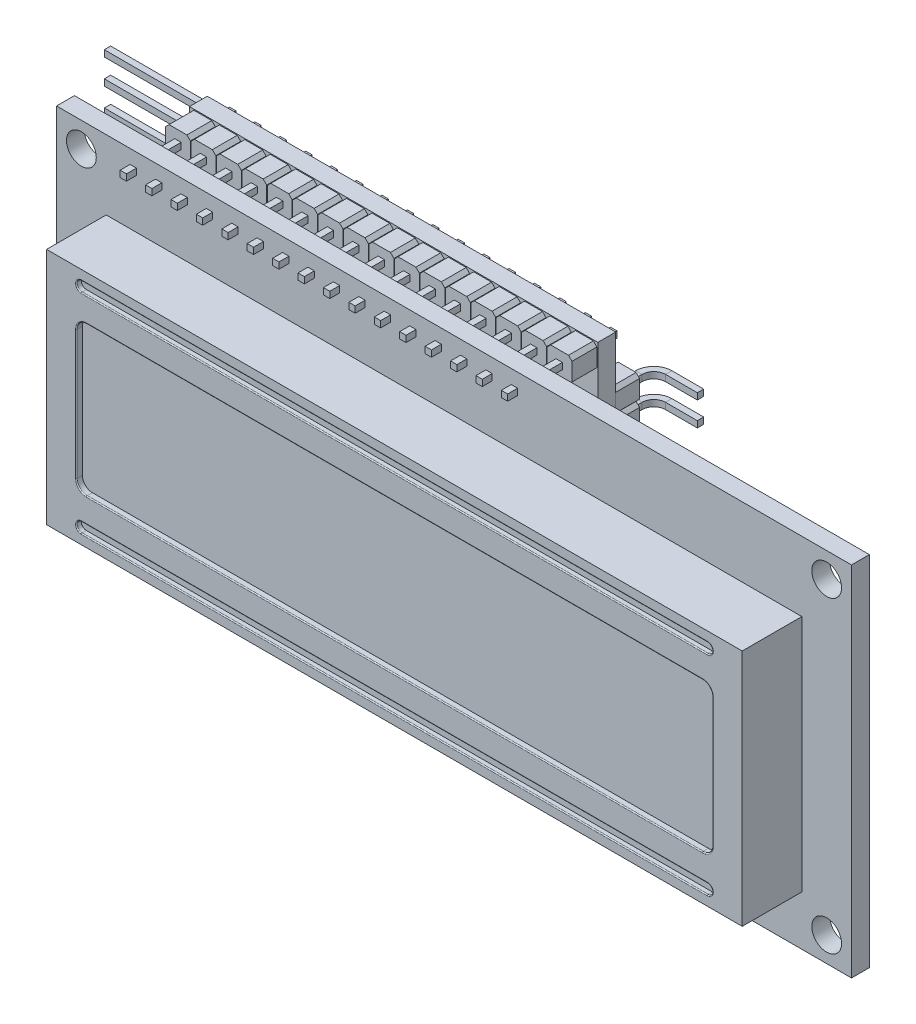
SolidWorks part; units mm, degrees
ref_plane "Front Plane" through (0, 0, 0) normal (0, 0, 1) x (1, 0, 0)
ref_plane "Top Plane" through (0, 0, 0) normal (0, 1, 0) x (1, 0, 0)
ref_plane "Right Plane" through (0, 0, 0) normal (1, 0, 0) x (0, 0, -1)
sketch "Sketch1" plane through (0, 0, 0) normal (0, 0, 1) x (1, 0, 0)
  line L0 (-40, 0) -> (40, 0) construction
  line L1 (-40, 18) -> (40, 18)
  line L2 (-40, 18) -> (-40, -18)
  line L3 (-40, -18) -> (40, -18)
  line L4 (40, 18) -> (40, -18)
  point P6 (0, 0)
  dimension "D1" = 80
  dimension "D2" = 36
extrude "silicon_chip" add sketch "Sketch1" along normal blind 1.8
sketch "Sketch2" plane through (0, 0, 1.8) normal (0, 0, 1) x (1, 0, 0)
  line L0 (40, 18) -> (-40, 18) construction
  line L1 (-40, 18) -> (-40, -18) construction
  line L2 (40, -18) -> (40, 18) construction
  line L3 (-40, -18) -> (40, -18) construction
  circle A0 centre (37.5, 15.5) radius 1.5
  circle A1 centre (37.5, -15.5) radius 1.5
  circle A2 centre (-37.5, -15.5) radius 1.5
  circle A3 centre (-37.5, 15.5) radius 1.5
  point P16 (0, 0)
  point P17 (0, 0)
  point P18 (0, 0)
  point P19 (0, 0)
  dimension "D1" = 3
  dimension "D4" = 2.5
  dimension "D5" = 2.5
  dimension "D2" = 2.5
  dimension "D3" = 2.5
extrude "screw_holes" cut sketch "Sketch2" against normal up to surface (1.8 mm away) up to face at (0, 0, 0)
sketch "Sketch3" plane through (0, 0, 1.8) normal (0, 0, 1) x (1, 0, 0)
  line L0 (-40, 18) -> (-40, -18) construction
  line L1 (-32.6, 16.6) -> (-31.9607, 16.6)
  line L2 (-32.6, 16.6) -> (-32.6, 15.9607)
  line L3 (-32.6, 15.9607) -> (-31.9607, 15.9607)
  line L4 (-31.9607, 16.6) -> (-31.9607, 15.9607)
  line L5 (40, 18) -> (-40, 18) construction
  line L6 (-29.4033, 16.6) -> (-29.4033, 15.9607)
  line L7 (-30.0426, 15.9607) -> (-29.4033, 15.9607)
  line L8 (-30.0426, 16.6) -> (-30.0426, 15.9607)
  line L9 (-30.0426, 16.6) -> (-29.4033, 16.6)
  line L10 (-26.8459, 16.6) -> (-26.8459, 15.9607)
  line L11 (-27.4852, 15.9607) -> (-26.8459, 15.9607)
  line L12 (-27.4852, 16.6) -> (-27.4852, 15.9607)
  line L13 (-27.4852, 16.6) -> (-26.8459, 16.6)
  line L14 (-24.2885, 16.6) -> (-24.2885, 15.9607)
  line L15 (-24.9279, 15.9607) -> (-24.2885, 15.9607)
  line L16 (-24.9279, 16.6) -> (-24.9279, 15.9607)
  line L17 (-24.9279, 16.6) -> (-24.2885, 16.6)
  line L18 (-21.7311, 16.6) -> (-21.7311, 15.9607)
  line L19 (-22.3705, 15.9607) -> (-21.7311, 15.9607)
  line L20 (-22.3705, 16.6) -> (-22.3705, 15.9607)
  line L21 (-22.3705, 16.6) -> (-21.7311, 16.6)
  line L22 (-19.1738, 16.6) -> (-19.1738, 15.9607)
  line L23 (-19.8131, 15.9607) -> (-19.1738, 15.9607)
  line L24 (-19.8131, 16.6) -> (-19.8131, 15.9607)
  line L25 (-19.8131, 16.6) -> (-19.1738, 16.6)
  line L26 (-16.6164, 16.6) -> (-16.6164, 15.9607)
  line L27 (-17.2557, 15.9607) -> (-16.6164, 15.9607)
  line L28 (-17.2557, 16.6) -> (-17.2557, 15.9607)
  line L29 (-17.2557, 16.6) -> (-16.6164, 16.6)
  line L30 (-14.059, 16.6) -> (-14.059, 15.9607)
  line L31 (-14.6984, 15.9607) -> (-14.059, 15.9607)
  line L32 (-14.6984, 16.6) -> (-14.6984, 15.9607)
  line L33 (-14.6984, 16.6) -> (-14.059, 16.6)
  line L34 (-11.5016, 16.6) -> (-11.5016, 15.9607)
  line L35 (-12.141, 15.9607) -> (-11.5016, 15.9607)
  line L36 (-12.141, 16.6) -> (-12.141, 15.9607)
  line L37 (-12.141, 16.6) -> (-11.5016, 16.6)
  line L38 (-8.9443, 16.6) -> (-8.9443, 15.9607)
  line L39 (-9.5836, 15.9607) -> (-8.9443, 15.9607)
  line L40 (-9.5836, 16.6) -> (-9.5836, 15.9607)
  line L41 (-9.5836, 16.6) -> (-8.9443, 16.6)
  line L42 (-6.3869, 16.6) -> (-6.3869, 15.9607)
  line L43 (-7.0262, 15.9607) -> (-6.3869, 15.9607)
  line L44 (-7.0262, 16.6) -> (-7.0262, 15.9607)
  line L45 (-7.0262, 16.6) -> (-6.3869, 16.6)
  line L46 (-3.8295, 16.6) -> (-3.8295, 15.9607)
  line L47 (-4.4689, 15.9607) -> (-3.8295, 15.9607)
  line L48 (-4.4689, 16.6) -> (-4.4689, 15.9607)
  line L49 (-4.4689, 16.6) -> (-3.8295, 16.6)
  line L50 (-1.2721, 16.6) -> (-1.2721, 15.9607)
  line L51 (-1.9115, 15.9607) -> (-1.2721, 15.9607)
  line L52 (-1.9115, 16.6) -> (-1.9115, 15.9607)
  line L53 (-1.9115, 16.6) -> (-1.2721, 16.6)
  line L54 (1.2852, 16.6) -> (1.2852, 15.9607)
  line L55 (0.6459, 15.9607) -> (1.2852, 15.9607)
  line L56 (0.6459, 16.6) -> (0.6459, 15.9607)
  line L57 (0.6459, 16.6) -> (1.2852, 16.6)
  line L58 (3.8426, 16.6) -> (3.8426, 15.9607)
  line L59 (3.2033, 15.9607) -> (3.8426, 15.9607)
  line L60 (3.2033, 16.6) -> (3.2033, 15.9607)
  line L61 (3.2033, 16.6) -> (3.8426, 16.6)
  line L62 (6.4, 16.6) -> (6.4, 15.9607)
  line L63 (5.7607, 15.9607) -> (6.4, 15.9607)
  line L64 (5.7607, 16.6) -> (5.7607, 15.9607)
  line L65 (5.7607, 16.6) -> (6.4, 16.6)
  point P8 (0, 0)
  dimension "D1" = 7.4
  dimension "D2" = 1.4
  dimension "D3" = 0.6393
  dimension "D5" = 39
  dimension "D4" = 16
extrude "pins" add sketch "Sketch3" along normal blind 1 and the other way blind 10
sketch "Sketch4" plane through (0, 0, 1.8) normal (0, 0, 1) x (1, 0, 0)
  line L0 (-33.1803, 17.5339) -> (-31.3803, 17.5339)
  line L1 (-31.3803, 17.5339) -> (-31.0268, 17.1803)
  line L3 (-31.0268, 15.3803) -> (-31.3803, 15.0268)
  line L4 (-31.3803, 15.0268) -> (-33.1803, 15.0268)
  line L5 (-33.1803, 15.0268) -> (-33.5339, 15.3803)
  line L6 (-33.5339, 15.3803) -> (-33.5339, 17.1803)
  line L7 (-33.5339, 17.1803) -> (-33.1803, 17.5339)
  line L8 (-32.2803, 15.0268) -> (-32.2803, 17.4318) construction
  line L9 (-31.9607, 16.6) -> (-32.6, 16.6) construction
  line L10 (-32.6, 16.6) -> (-32.6, 15.9607) construction
  line L12 (-33.5339, 16.2803) -> (-31.101, 16.2803) construction
  line L104 (-31.0268, 17.1803) -> (-31.0268, 15.3803)
  line L105 (-30.6203, 17.5339) -> (-28.8203, 17.5339)
  line L106 (-28.8203, 17.5339) -> (-28.4668, 17.1803)
  line L107 (-28.4668, 15.3803) -> (-28.8203, 15.0268)
  line L108 (-28.8203, 15.0268) -> (-30.6203, 15.0268)
  line L109 (-30.6203, 15.0268) -> (-30.9739, 15.3803)
  line L110 (-30.9739, 15.3803) -> (-30.9739, 17.1803)
  line L111 (-30.9739, 17.1803) -> (-30.6203, 17.5339)
  line L112 (-28.4668, 17.1803) -> (-28.4668, 15.3803)
  line L113 (-29.7203, 15.0268) -> (-29.7203, 17.4318) construction
  line L114 (-30.9739, 16.2803) -> (-28.541, 16.2803) construction
  line L115 (-28.0603, 17.5339) -> (-26.2603, 17.5339)
  line L116 (-26.2603, 17.5339) -> (-25.9068, 17.1803)
  line L117 (-25.9068, 15.3803) -> (-26.2603, 15.0268)
  line L118 (-26.2603, 15.0268) -> (-28.0603, 15.0268)
  line L119 (-28.0603, 15.0268) -> (-28.4139, 15.3803)
  line L120 (-28.4139, 15.3803) -> (-28.4139, 17.1803)
  line L121 (-28.4139, 17.1803) -> (-28.0603, 17.5339)
  line L122 (-25.9068, 17.1803) -> (-25.9068, 15.3803)
  line L123 (-27.1603, 15.0268) -> (-27.1603, 17.4318) construction
  line L124 (-28.4139, 16.2803) -> (-25.981, 16.2803) construction
  line L125 (-25.5003, 17.5339) -> (-23.7003, 17.5339)
  line L126 (-23.7003, 17.5339) -> (-23.3468, 17.1803)
  line L127 (-23.3468, 15.3803) -> (-23.7003, 15.0268)
  line L128 (-23.7003, 15.0268) -> (-25.5003, 15.0268)
  line L129 (-25.5003, 15.0268) -> (-25.8539, 15.3803)
  line L130 (-25.8539, 15.3803) -> (-25.8539, 17.1803)
  line L131 (-25.8539, 17.1803) -> (-25.5003, 17.5339)
  line L132 (-23.3468, 17.1803) -> (-23.3468, 15.3803)
  line L133 (-24.6003, 15.0268) -> (-24.6003, 17.4318) construction
  line L134 (-25.8539, 16.2803) -> (-23.421, 16.2803) construction
  line L135 (-22.9403, 17.5339) -> (-21.1403, 17.5339)
  line L136 (-21.1403, 17.5339) -> (-20.7868, 17.1803)
  line L137 (-20.7868, 15.3803) -> (-21.1403, 15.0268)
  line L138 (-21.1403, 15.0268) -> (-22.9403, 15.0268)
  line L139 (-22.9403, 15.0268) -> (-23.2939, 15.3803)
  line L140 (-23.2939, 15.3803) -> (-23.2939, 17.1803)
  line L141 (-23.2939, 17.1803) -> (-22.9403, 17.5339)
  line L142 (-20.7868, 17.1803) -> (-20.7868, 15.3803)
  line L143 (-22.0403, 15.0268) -> (-22.0403, 17.4318) construction
  line L144 (-23.2939, 16.2803) -> (-20.861, 16.2803) construction
  line L145 (-20.3803, 17.5339) -> (-18.5803, 17.5339)
  line L146 (-18.5803, 17.5339) -> (-18.2268, 17.1803)
  line L147 (-18.2268, 15.3803) -> (-18.5803, 15.0268)
  line L148 (-18.5803, 15.0268) -> (-20.3803, 15.0268)
  line L149 (-20.3803, 15.0268) -> (-20.7339, 15.3803)
  line L150 (-20.7339, 15.3803) -> (-20.7339, 17.1803)
  line L151 (-20.7339, 17.1803) -> (-20.3803, 17.5339)
  line L152 (-18.2268, 17.1803) -> (-18.2268, 15.3803)
  line L153 (-19.4803, 15.0268) -> (-19.4803, 17.4318) construction
  line L154 (-20.7339, 16.2803) -> (-18.301, 16.2803) construction
  line L155 (-17.8203, 17.5339) -> (-16.0203, 17.5339)
  line L156 (-16.0203, 17.5339) -> (-15.6668, 17.1803)
  line L157 (-15.6668, 15.3803) -> (-16.0203, 15.0268)
  line L158 (-16.0203, 15.0268) -> (-17.8203, 15.0268)
  line L159 (-17.8203, 15.0268) -> (-18.1739, 15.3803)
  line L160 (-18.1739, 15.3803) -> (-18.1739, 17.1803)
  line L161 (-18.1739, 17.1803) -> (-17.8203, 17.5339)
  line L162 (-15.6668, 17.1803) -> (-15.6668, 15.3803)
  line L163 (-16.9203, 15.0268) -> (-16.9203, 17.4318) construction
  line L164 (-18.1739, 16.2803) -> (-15.741, 16.2803) construction
  line L165 (-15.2603, 17.5339) -> (-13.4603, 17.5339)
  line L166 (-13.4603, 17.5339) -> (-13.1068, 17.1803)
  line L167 (-13.1068, 15.3803) -> (-13.4603, 15.0268)
  line L168 (-13.4603, 15.0268) -> (-15.2603, 15.0268)
  line L169 (-15.2603, 15.0268) -> (-15.6139, 15.3803)
  line L170 (-15.6139, 15.3803) -> (-15.6139, 17.1803)
  line L171 (-15.6139, 17.1803) -> (-15.2603, 17.5339)
  line L172 (-13.1068, 17.1803) -> (-13.1068, 15.3803)
  line L173 (-14.3603, 15.0268) -> (-14.3603, 17.4318) construction
  line L174 (-15.6139, 16.2803) -> (-13.181, 16.2803) construction
  line L175 (-12.7003, 17.5339) -> (-10.9003, 17.5339)
  line L176 (-10.9003, 17.5339) -> (-10.5468, 17.1803)
  line L177 (-10.5468, 15.3803) -> (-10.9003, 15.0268)
  line L178 (-10.9003, 15.0268) -> (-12.7003, 15.0268)
  line L179 (-12.7003, 15.0268) -> (-13.0539, 15.3803)
  line L180 (-13.0539, 15.3803) -> (-13.0539, 17.1803)
  line L181 (-13.0539, 17.1803) -> (-12.7003, 17.5339)
  line L182 (-10.5468, 17.1803) -> (-10.5468, 15.3803)
  line L183 (-11.8003, 15.0268) -> (-11.8003, 17.4318) construction
  line L184 (-13.0539, 16.2803) -> (-10.621, 16.2803) construction
  line L185 (-10.1403, 17.5339) -> (-8.3403, 17.5339)
  line L186 (-8.3403, 17.5339) -> (-7.9868, 17.1803)
  line L187 (-7.9868, 15.3803) -> (-8.3403, 15.0268)
  line L188 (-8.3403, 15.0268) -> (-10.1403, 15.0268)
  line L189 (-10.1403, 15.0268) -> (-10.4939, 15.3803)
  line L190 (-10.4939, 15.3803) -> (-10.4939, 17.1803)
  line L191 (-10.4939, 17.1803) -> (-10.1403, 17.5339)
  line L192 (-7.9868, 17.1803) -> (-7.9868, 15.3803)
  line L193 (-9.2403, 15.0268) -> (-9.2403, 17.4318) construction
  line L194 (-10.4939, 16.2803) -> (-8.061, 16.2803) construction
  line L195 (-7.5803, 17.5339) -> (-5.7803, 17.5339)
  line L196 (-5.7803, 17.5339) -> (-5.4268, 17.1803)
  line L197 (-5.4268, 15.3803) -> (-5.7803, 15.0268)
  line L198 (-5.7803, 15.0268) -> (-7.5803, 15.0268)
  line L199 (-7.5803, 15.0268) -> (-7.9339, 15.3803)
  line L200 (-7.9339, 15.3803) -> (-7.9339, 17.1803)
  line L201 (-7.9339, 17.1803) -> (-7.5803, 17.5339)
  line L202 (-5.4268, 17.1803) -> (-5.4268, 15.3803)
  line L203 (-6.6803, 15.0268) -> (-6.6803, 17.4318) construction
  line L204 (-7.9339, 16.2803) -> (-5.501, 16.2803) construction
  line L205 (-5.0203, 17.5339) -> (-3.2203, 17.5339)
  line L206 (-3.2203, 17.5339) -> (-2.8668, 17.1803)
  line L207 (-2.8668, 15.3803) -> (-3.2203, 15.0268)
  line L208 (-3.2203, 15.0268) -> (-5.0203, 15.0268)
  line L209 (-5.0203, 15.0268) -> (-5.3739, 15.3803)
  line L210 (-5.3739, 15.3803) -> (-5.3739, 17.1803)
  line L211 (-5.3739, 17.1803) -> (-5.0203, 17.5339)
  line L212 (-2.8668, 17.1803) -> (-2.8668, 15.3803)
  line L213 (-4.1203, 15.0268) -> (-4.1203, 17.4318) construction
  line L214 (-5.3739, 16.2803) -> (-2.941, 16.2803) construction
  line L215 (-2.4603, 17.5339) -> (-0.6603, 17.5339)
  line L216 (-0.6603, 17.5339) -> (-0.3068, 17.1803)
  line L217 (-0.3068, 15.3803) -> (-0.6603, 15.0268)
  line L218 (-0.6603, 15.0268) -> (-2.4603, 15.0268)
  line L219 (-2.4603, 15.0268) -> (-2.8139, 15.3803)
  line L220 (-2.8139, 15.3803) -> (-2.8139, 17.1803)
  line L221 (-2.8139, 17.1803) -> (-2.4603, 17.5339)
  line L222 (-0.3068, 17.1803) -> (-0.3068, 15.3803)
  line L223 (-1.5603, 15.0268) -> (-1.5603, 17.4318) construction
  line L224 (-2.8139, 16.2803) -> (-0.381, 16.2803) construction
  line L225 (0.0997, 17.5339) -> (1.8997, 17.5339)
  line L226 (1.8997, 17.5339) -> (2.2532, 17.1803)
  line L227 (2.2532, 15.3803) -> (1.8997, 15.0268)
  line L228 (1.8997, 15.0268) -> (0.0997, 15.0268)
  line L229 (0.0997, 15.0268) -> (-0.2539, 15.3803)
  line L230 (-0.2539, 15.3803) -> (-0.2539, 17.1803)
  line L231 (-0.2539, 17.1803) -> (0.0997, 17.5339)
  line L232 (2.2532, 17.1803) -> (2.2532, 15.3803)
  line L233 (0.9997, 15.0268) -> (0.9997, 17.4318) construction
  line L234 (-0.2539, 16.2803) -> (2.179, 16.2803) construction
  line L235 (2.6597, 17.5339) -> (4.4597, 17.5339)
  line L236 (4.4597, 17.5339) -> (4.8132, 17.1803)
  line L237 (4.8132, 15.3803) -> (4.4597, 15.0268)
  line L238 (4.4597, 15.0268) -> (2.6597, 15.0268)
  line L239 (2.6597, 15.0268) -> (2.3061, 15.3803)
  line L240 (2.3061, 15.3803) -> (2.3061, 17.1803)
  line L241 (2.3061, 17.1803) -> (2.6597, 17.5339)
  line L242 (4.8132, 17.1803) -> (4.8132, 15.3803)
  line L243 (3.5597, 15.0268) -> (3.5597, 17.4318) construction
  line L244 (2.3061, 16.2803) -> (4.739, 16.2803) construction
  line L245 (5.2197, 17.5339) -> (7.0197, 17.5339)
  line L246 (7.0197, 17.5339) -> (7.3732, 17.1803)
  line L247 (7.3732, 15.3803) -> (7.0197, 15.0268)
  line L248 (7.0197, 15.0268) -> (5.2197, 15.0268)
  line L249 (5.2197, 15.0268) -> (4.8661, 15.3803)
  line L250 (4.8661, 15.3803) -> (4.8661, 17.1803)
  line L251 (4.8661, 17.1803) -> (5.2197, 17.5339)
  line L252 (7.3732, 17.1803) -> (7.3732, 15.3803)
  line L253 (6.1197, 15.0268) -> (6.1197, 17.4318) construction
  line L254 (4.8661, 16.2803) -> (7.299, 16.2803) construction
  point P10 (-32.3175, 16.2803)
  point P13 (-32.2803, 16.6)
  point P16 (-32.6, 16.2803)
  point P17 (0, 0)
  point P18 (-32.2803, 16.2293)
  point P21 (0, 0)
  point P202 (0, 0)
  point P203 (0, 0)
  dimension "D1" = 135
  dimension "D2" = 135
  dimension "D3" = 0.5
  dimension "D4" = 1.8
  dimension "D6" = 0.0529
  dimension "D7" = 2.4329
  dimension "D8" = 2.405
  dimension "D5" = 16
extrude "pin_holders" add sketch "Sketch4" against normal blind 2.5 from offset 4.5 offset against normal yes
sketch "Sketch5" plane through (0, 0, -5.2) normal (0, 0, -1) x (-1, 0, 0)
  line L0 (-7.0197, 17.5339) -> (-5.2197, 17.5339) construction
  line L1 (-7.4732, 17.6339) -> (33.6268, 17.6339)
  line L2 (-7.4732, 17.6339) -> (-7.4732, -0.3661)
  line L3 (-7.4732, -0.3661) -> (33.6268, -0.3661)
  line L4 (33.6268, 17.6339) -> (33.6268, -0.3661)
  line L5 (-7.3732, 15.3803) -> (-7.3732, 17.1803) construction
  dimension "D1" = 18
  dimension "D2" = 41.1
  dimension "D3" = 0.1
  dimension "D4" = 0.1
extrude "silicon_chip_2" add sketch "Sketch5" along normal blind 1.8
sketch "Sketch6" plane through (0, 0, -7) normal (0, 0, -1) x (-1, 0, 0)
  line L0 (33.6268, 17.6339) -> (-7.4732, 17.6339) construction
  line L1 (21.6268, 12.6339) -> (28.6268, 12.6339)
  line L2 (21.6268, 12.6339) -> (21.6268, 5.6339)
  line L3 (21.6268, 5.6339) -> (28.6268, 5.6339)
  line L4 (28.6268, 12.6339) -> (28.6268, 5.6339)
  line L5 (33.6268, -0.3661) -> (33.6268, 17.6339) construction
  dimension "D1" = 5
  dimension "D2" = 5
  dimension "D3" = 7
  dimension "D4" = 7
extrude "variable_resistor" add sketch "Sketch6" along normal blind 5
sketch "Sketch7" plane through (0, 0, -12) normal (0, 0, -1) x (-1, 0, 0)
  line L0 (25.3768, 9.3839) -> (26.3768, 9.3839)
  line L1 (24.8768, 10.3839) -> (25.3768, 10.3839)
  line L2 (24.8768, 10.3839) -> (24.8768, 9.3839)
  line L3 (24.8768, 7.8839) -> (25.3768, 7.8839)
  line L4 (25.3768, 10.3839) -> (25.3768, 9.3839)
  line L5 (23.8768, 9.3839) -> (24.8768, 9.3839)
  line L6 (23.8768, 9.3839) -> (23.8768, 8.8839)
  line L7 (23.8768, 8.8839) -> (24.8768, 8.8839)
  line L8 (26.3768, 9.3839) -> (26.3768, 8.8839)
  line L9 (24.8768, 8.8839) -> (24.8768, 7.8839)
  line L10 (25.3768, 8.8839) -> (25.3768, 7.8839)
  line L11 (25.3768, 8.8839) -> (26.3768, 8.8839)
  line L12 (25.1268, 12.6339) -> (25.1268, 5.6339) construction
  line L13 (28.6268, 12.6339) -> (21.6268, 12.6339) construction
  line L14 (21.6268, 5.6339) -> (28.6268, 5.6339) construction
  line L15 (23.8768, 9.1339) -> (26.3768, 9.1339) construction
  point P12 (26.8356, 9.321)
  point P21 (25.1268, 9.1339)
  point P22 (25.1268, 9.1339)
  point P23 (0, 0)
  dimension "D1" = 0.5
  dimension "D2" = 1
extrude "screwdriver_hole_lvl_2" cut sketch "Sketch7" against normal blind 1
sketch "Sketch8" plane through (0, 0, -12) normal (0, 0, -1) x (-1, 0, 0)
  line L0 (25.1268, 12.6339) -> (25.1268, 5.6339) construction
  line L1 (28.6268, 12.6339) -> (21.6268, 12.6339) construction
  line L2 (21.6268, 5.6339) -> (28.6268, 5.6339) construction
  circle A0 centre (25.1268, 9.1339) radius 1.3
  point P8 (0, 0)
  point P9 (25.1268, 9.1339)
  dimension "D1" = 2.6
extrude "screw_driver_hole_lvl_1" cut sketch "Sketch8" against normal blind 0.1
sketch "Sketch9" plane through (0, 0, -7) normal (0, 0, -1) x (-1, 0, 0)
  line L0 (31.3732, 12.6339) -> (33.1732, 12.6339)
  line L1 (33.1732, 12.6339) -> (33.5268, 12.2803)
  line L3 (33.5268, 10.4803) -> (33.1732, 10.1268)
  line L4 (33.1732, 10.1268) -> (31.3732, 10.1268)
  line L5 (31.3732, 10.1268) -> (31.0197, 10.4803)
  line L6 (31.0197, 10.4803) -> (31.0197, 12.2803)
  line L7 (31.0197, 12.2803) -> (31.3732, 12.6339)
  line L8 (32.2732, 10.1268) -> (32.2732, 12.6339) construction
  line L9 (33.6268, -0.3661) -> (33.6268, 17.6339) construction
  line L12 (31.0197, 11.3803) -> (33.5268, 11.3803) construction
  line L104 (33.5268, 12.2803) -> (33.5268, 10.4803)
  line L105 (28.6268, 12.6339) -> (21.6268, 12.6339) construction
  line L106 (33.5268, 7.9632) -> (33.1732, 7.6097)
  line L107 (33.5268, 9.7632) -> (33.5268, 7.9632)
  line L108 (33.1732, 10.1168) -> (33.5268, 9.7632)
  line L109 (31.3732, 10.1168) -> (33.1732, 10.1168)
  line L110 (31.0197, 9.7632) -> (31.3732, 10.1168)
  line L111 (31.0197, 7.9632) -> (31.0197, 9.7632)
  line L112 (31.3732, 7.6097) -> (31.0197, 7.9632)
  line L113 (33.1732, 7.6097) -> (31.3732, 7.6097)
  line L114 (33.5268, 5.4461) -> (33.1732, 5.0926)
  line L115 (33.5268, 7.2461) -> (33.5268, 5.4461)
  line L116 (33.1732, 7.5997) -> (33.5268, 7.2461)
  line L117 (31.3732, 7.5997) -> (33.1732, 7.5997)
  line L118 (31.0197, 7.2461) -> (31.3732, 7.5997)
  line L119 (31.0197, 5.4461) -> (31.0197, 7.2461)
  line L120 (31.3732, 5.0926) -> (31.0197, 5.4461)
  line L121 (33.1732, 5.0926) -> (31.3732, 5.0926)
  line L122 (33.5268, 2.929) -> (33.1732, 2.5755)
  line L123 (33.5268, 4.729) -> (33.5268, 2.929)
  line L124 (33.1732, 5.0826) -> (33.5268, 4.729)
  line L125 (31.3732, 5.0826) -> (33.1732, 5.0826)
  line L126 (31.0197, 4.729) -> (31.3732, 5.0826)
  line L127 (31.0197, 2.929) -> (31.0197, 4.729)
  line L128 (31.3732, 2.5755) -> (31.0197, 2.929)
  line L129 (33.1732, 2.5755) -> (31.3732, 2.5755)
  point P10 (32.2732, 11.3803)
  point P18 (32.2732, 11.3803)
  dimension "D1" = 0.5
  dimension "D2" = 1.8
  dimension "D3" = 0.1
  dimension "D4" = 4
  dimension "D5" = 0.01
extrude "pinholders_2" add sketch "Sketch9" along normal blind 2.5
sketch "Sketch11" plane through (0, 0, -9.5) normal (0, 0, -1) x (-1, 0, 0)
  line L0 (32.2732, 12.6339) -> (32.2732, 10.1268) construction
  line L1 (31.9532, 11.7003) -> (32.5932, 11.7003)
  line L2 (31.9532, 11.7003) -> (31.9532, 11.0603)
  line L3 (31.9532, 11.0603) -> (32.5932, 11.0603)
  line L4 (32.5932, 11.7003) -> (32.5932, 11.0603)
  line L5 (33.1732, 12.6339) -> (31.3732, 12.6339) construction
  line L6 (31.3732, 10.1268) -> (33.1732, 10.1268) construction
  line L7 (32.2732, 11.7003) -> (32.2732, 11.0603) construction
  point P12 (32.2732, 10.1268)
  point P13 (32.2732, 10.1268)
  point P14 (32.2732, 11.3803)
  point P15 (32.2732, 11.3803)
  dimension "D1" = 0.64
ref_plane "Plane1" through (0, 11.3755, 0) normal (0, -1, 0) x (-1, 0, 0)
sketch "Sketch10" plane through (0, 11.3755, 0) normal (0, -1, 0) x (-1, 0, 0)
  line L0 (32.3, 8.6) -> (32.3, 10.6)
  line L1 (33.8, 12.1) -> (48.8, 12.1)
  arc A0 (32.3, 10.6) -> (33.8, 12.1) centre (33.8, 10.6) cw
  dimension "D2" = 1.5
  dimension "D1" = 15
  dimension "D3" = 2
  dimension "D4" = 8.6
  dimension "D5" = 32.3
sweep "bent_pin" add profiles "Sketch11" path "Sketch10"
pattern_linear "bent_pins" count 4 spacing 2.54 along (0, -1, 0) of "bent_pin"
sketch "Sketch12" plane through (0, 0, -7) normal (0, 0, -1) x (-1, 0, 0)
  line L0 (28.6268, 12.6339) -> (21.6268, 12.6339) construction
  line L1 (10.6268, 12.6339) -> (17.6268, 12.6339)
  line L2 (10.6268, 12.6339) -> (10.6268, 2.6339)
  line L3 (10.6268, 2.6339) -> (17.6268, 2.6339)
  line L4 (17.6268, 12.6339) -> (17.6268, 2.6339)
  line L5 (21.6268, 12.6339) -> (21.6268, 5.6339) construction
  point P8 (21.6268, 9.1339)
  dimension "D1" = 7
  dimension "D2" = 10
  dimension "D3" = 4
extrude "ic" add sketch "Sketch12" along normal blind 2
ref_plane "Plane2" through (0, 3.6339, 0) normal (0, -1, 0) x (-1, 0, 0)
sketch "Sketch13" plane through (0, 3.6339, 0) normal (0, -1, 0) x (-1, 0, 0)
  line L0 (17.3, 8.4) -> (17.8, 8.4)
  line L1 (18.2, 8) -> (18.2, 7.4)
  line L2 (18.6, 7) -> (18.8, 7)
  arc A0 (17.8, 8.4) -> (18.2, 8) centre (17.8, 8) cw
  arc A1 (18.2, 7.4) -> (18.6, 7) centre (18.6, 7.4) ccw
  dimension "D1" = 0.4
  dimension "D2" = 0.4
  dimension "D3" = 0.5
  dimension "D4" = 0.6
  dimension "D5" = 0.2
  dimension "D6" = 8.4
  dimension "D7" = 17.3
sketch "Sketch14" plane through (-17.6268, 0, 0) normal (-1, 0, 0) x (0, 0, 1)
  line L0 (-8.4, 3.8839) -> (-8.4, 3.3839) construction
  line L1 (-8.65, 3.8839) -> (-8.15, 3.8839)
  line L2 (-8.65, 3.8839) -> (-8.65, 3.3839)
  line L3 (-8.65, 3.3839) -> (-8.15, 3.3839)
  line L4 (-8.15, 3.8839) -> (-8.15, 3.3839)
  point P6 (-8.4, 3.6339)
  dimension "D1" = 0.5
sweep "IC_pin" add profiles "Sketch14" path "Sketch13"
pattern_linear "IC_pins_1" count 8 spacing 1.1 along (0, 1, 0) of "IC_pin"
sketch "Sketch15" plane through (0, 0, -9) normal (0, 0, -1) x (-1, 0, 0)
  line L0 (14.1268, 12.6339) -> (14.1268, 2.6339) construction
  line L1 (17.6268, 12.6339) -> (10.6268, 12.6339) construction
  line L2 (10.6268, 2.6339) -> (17.6268, 2.6339) construction
ref_plane "Plane3" through (-14.1268, 0, 0) normal (1, 0, 0) x (0, -1, 0)
mirror "IC_pins_2" about plane through (-14.1268, 0, 0) normal (1, 0, 0) of "IC_pins_1"
sketch "Sketch16" plane through (0, 0, -7) normal (0, 0, -1) x (-1, 0, 0)
  line L0 (-7.0197, 12.6339) -> (-5.2197, 12.6339)
  line L1 (-5.2197, 12.6339) -> (-4.8661, 12.2803)
  line L3 (-4.8661, 10.4803) -> (-5.2197, 10.1268)
  line L4 (-5.2197, 10.1268) -> (-7.0197, 10.1268)
  line L5 (-7.0197, 10.1268) -> (-7.3732, 10.4803)
  line L6 (-7.3732, 10.4803) -> (-7.3732, 12.2803)
  line L7 (-7.3732, 12.2803) -> (-7.0197, 12.6339)
  line L8 (-6.1197, 10.1268) -> (-6.1197, 12.6339) construction
  line L10 (33.6268, 17.6339) -> (-7.4732, 17.6339) construction
  line L12 (-7.3732, 11.3803) -> (-4.8661, 11.3803) construction
  line L104 (-4.8661, 12.2803) -> (-4.8661, 10.4803)
  line L106 (-4.8661, 7.9632) -> (-5.2197, 7.6097)
  line L107 (-4.8661, 9.7632) -> (-4.8661, 7.9632)
  line L108 (-5.2197, 10.1168) -> (-4.8661, 9.7632)
  line L109 (-7.0197, 10.1168) -> (-5.2197, 10.1168)
  line L110 (-7.3732, 9.7632) -> (-7.0197, 10.1168)
  line L111 (-7.3732, 7.9632) -> (-7.3732, 9.7632)
  line L112 (-7.0197, 7.6097) -> (-7.3732, 7.9632)
  line L113 (-5.2197, 7.6097) -> (-7.0197, 7.6097)
  line L130 (-4.8661, 5.4461) -> (-5.2197, 5.0926) [skipped]
  line L131 (-4.8661, 7.2461) -> (-4.8661, 5.4461) [skipped]
  line L132 (-5.2197, 7.5997) -> (-4.8661, 7.2461) [skipped]
  line L133 (-7.3732, 7.2461) -> (-7.0197, 7.5997) [skipped]
  line L134 (-7.3732, 5.4461) -> (-7.3732, 7.2461) [skipped]
  line L135 (-7.0197, 5.0926) -> (-7.3732, 5.4461) [skipped]
  line L136 (-5.2197, 5.0926) -> (-7.0197, 5.0926) [skipped]
  line L137 (-4.8661, 2.929) -> (-5.2197, 2.5755) [skipped]
  line L138 (-4.8661, 4.729) -> (-4.8661, 2.929) [skipped]
  line L139 (-5.2197, 5.0826) -> (-4.8661, 4.729) [skipped]
  line L140 (-7.0197, 5.0826) -> (-5.2197, 5.0826) [skipped]
  line L141 (-7.3732, 4.729) -> (-7.0197, 5.0826) [skipped]
  line L142 (-7.3732, 2.929) -> (-7.3732, 4.729) [skipped]
  line L143 (-7.0197, 2.5755) -> (-7.3732, 2.929) [skipped]
  line L144 (-5.2197, 2.5755) -> (-7.0197, 2.5755) [skipped]
  line L145 (-7.0197, 7.5997) -> (-5.2197, 7.5997) [skipped]
  line L146 (-7.4732, 17.6339) -> (-7.4732, -0.3661) construction
  dimension "D1" = 0.5
  dimension "D2" = 1.8
  dimension "D3" = 5
  dimension "D4" = 4
  dimension "D6" = 0.1
  dimension "D5" = 0.01
extrude "pinholders_3" add sketch "Sketch16" along normal blind 2.5
ref_plane "Plane4" through (0, 8.9097, 0) normal (0, -1, 0) x (-1, 0, 0)
sketch "Sketch19" plane through (0, 8.9097, 0) normal (0, -1, 0) x (-1, 0, 0)
  line L0 (-6.2, 8.3) -> (-6.2, 10.6042)
  line L1 (-7.7, 12.1042) -> (-10.9, 12.1042)
  arc A0 (-6.2, 10.6042) -> (-7.7, 12.1042) centre (-7.7, 10.6042) ccw
  dimension "D1" = 1.5
  dimension "D2" = 8.3
  dimension "D3" = 6.2
  dimension "D4" = 2.3042
  dimension "D5" = 3.2
sketch "Sketch20" plane through (0, 0, -9.5) normal (0, 0, -1) x (-1, 0, 0)
  line L0 (-6.2, 9.2297) -> (-6.2, 8.5897) construction
  line L1 (-6.52, 9.2297) -> (-5.88, 9.2297)
  line L2 (-6.52, 9.2297) -> (-6.52, 8.5897)
  line L3 (-6.52, 8.5897) -> (-5.88, 8.5897)
  line L4 (-5.88, 9.2297) -> (-5.88, 8.5897)
  point P6 (-6.2, 8.9097)
  dimension "D1" = 0.64
sweep "bent_pin_2" add profiles "Sketch20" path "Sketch19"
mirror "bent_pins_2" about plane through (5.2197, 10.1268, -9.5) normal (0, 1, 0) of "bent_pin_2"
sketch "Sketch21" plane through (0, 0, 1.8) normal (0, 0, 1) x (1, 0, 0)
  line L1 (-35, 11) -> (35, 11)
  line L2 (-35, 11) -> (-35, -13)
  line L3 (-35, -13) -> (35, -13)
  line L4 (35, 11) -> (35, -13)
  dimension "D1" = 5
  dimension "D2" = 5
  dimension "D3" = 70
  dimension "D4" = 24
extrude "display_body" add sketch "Sketch21" along normal blind 6
sketch "Sketch22" plane through (0, 0, 7.8) normal (0, 0, 1) x (1, 0, 0)
  line L0 (-31.5, 10) -> (31.5, 10)
  line L1 (31.5, 9) -> (-31.5, 9)
  line L2 (35, 11) -> (-35, 11) construction
  line L3 (-35, 11) -> (-35, -13) construction
  line L4 (35, -13) -> (35, 11) construction
  line L5 (-35, -1) -> (35, -1) construction
  line L6 (31.5, -11) -> (-31.5, -11)
  line L7 (-31.5, -12) -> (31.5, -12)
  line L9 (-31, 6.5) -> (31, 6.5)
  line L10 (-32, 5.5) -> (-32, -7.5)
  line L11 (-31, -8.5) -> (31, -8.5)
  line L12 (32, 5.5) -> (32, -7.5)
  arc A0 (31.5, 10) -> (31.5, 9) centre (31.5, 9.5) cw
  arc A1 (-31.5, 9) -> (-31.5, 10) centre (-31.5, 9.5) cw
  arc A2 (31.5, -12) -> (31.5, -11) centre (31.5, -11.5) ccw
  arc A3 (-31.5, -11) -> (-31.5, -12) centre (-31.5, -11.5) ccw
  arc A4 (31, 6.5) -> (32, 5.5) centre (31, 5.5) cw
  arc A5 (31, -8.5) -> (32, -7.5) centre (31, -7.5) ccw
  arc A6 (-32, -7.5) -> (-31, -8.5) centre (-31, -7.5) ccw
  arc A7 (-31, 6.5) -> (-32, 5.5) centre (-31, 5.5) ccw
  dimension "D9" = 1
  dimension "D1" = 1
  dimension "D2" = 1
  dimension "D3" = 3.5
  dimension "D4" = 3.5
  dimension "D5" = 2.5
  dimension "D6" = 2.5
  dimension "D7" = 3
  dimension "D8" = 3
extrude "display_cuts" cut sketch "Sketch22" against normal blind 0.5
fillet "Fillet1" radius 0.1 16 edges at (0, 10, 7.8) (32, 9.5, 7.8) (0, 9, 7.8) (-32, -1, 7.8) (-31.7071, 6.2071, 7.8) (0, 6.5, 7.8) (31.7071, 6.2071, 7.8) (32, -1, 7.8) (31.7071, -8.2071, 7.8) (0, -8.5, 7.8) (0, -11, 7.8) (32, -11.5, 7.8) (0, -12, 7.8) (-32, 9.5, 7.8) (-31.7071, -8.2071, 7.8) (-32, -11.5, 7.8)
sketch "Sketch24" plane through (0, 0, 7.3) normal (0, 0, 1) x (1, 0, 0)
  line L0 (-31, 6.5) -> (31, 6.5)
  line L1 (32, 5.5) -> (32, -7.5)
  line L2 (31, -8.5) -> (-31, -8.5)
  line L3 (-32, -7.5) -> (-32, 5.5)
  arc A0 (31, 6.5) -> (32, 5.5) centre (31, 5.5) cw
  arc A1 (32, -7.5) -> (31, -8.5) centre (31, -7.5) cw
  arc A2 (-31, -8.5) -> (-32, -7.5) centre (-31, -7.5) cw
  arc A3 (-32, 5.5) -> (-31, 6.5) centre (-31, 5.5) cw
extrude "display_screen" cut sketch "Sketch24" against normal blind 0.1
